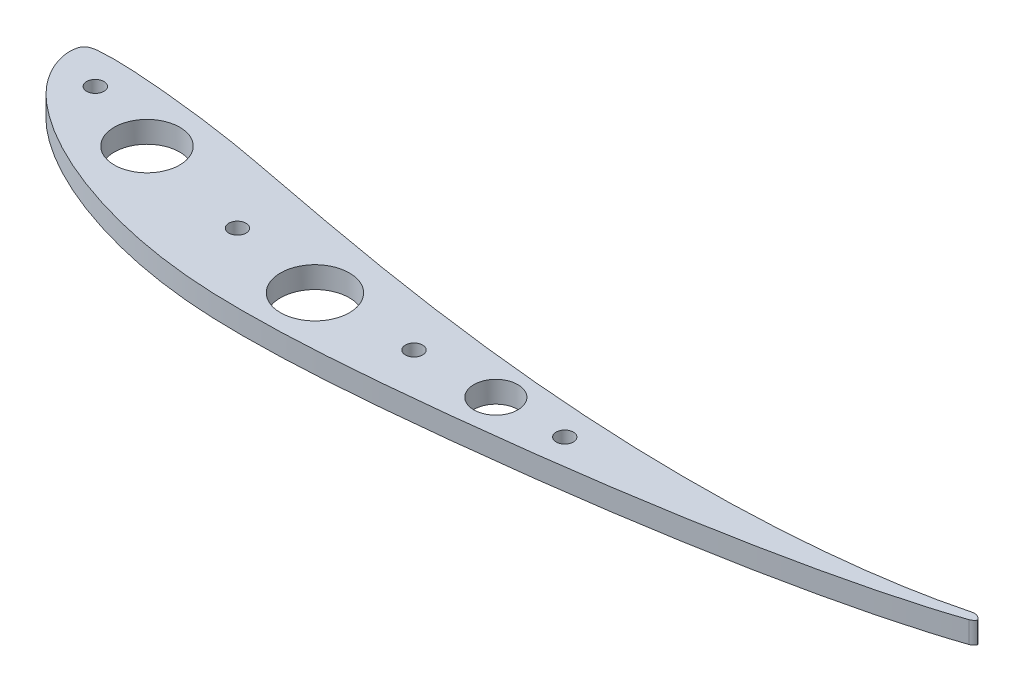
SolidWorks part; units mm, degrees
material "6061-T6 (SS)"
ref_plane "Front Plane" through (0, 0, 0) normal (0, 0, 1) x (1, 0, 0)
ref_plane "Top Plane" through (0, 0, 0) normal (0, 1, 0) x (1, 0, 0)
ref_plane "Right Plane" through (0, 0, 0) normal (1, 0, 0) x (0, 0, -1)
curve "Curve1"
  spline degree 3 poles (-3.7953, 0, -0.0099) (-3.8135, 0, 0.0025) (-3.7975, 0, -0.0094) (-3.7869, 0, -0.0198) (-3.7634, 0, -0.0415) (-3.7356, 0, -0.0646) (-3.6977, 0, -0.0879) (-3.6505, 0, -0.1105) (-3.5935, 0, -0.134) (-3.5268, 0, -0.1582) (-3.4508, 0, -0.1829) (-3.3657, 0, -0.2079) (-3.2722, 0, -0.233) (-3.1706, 0, -0.258) (-3.0616, 0, -0.2828) (-2.9459, 0, -0.3071) (-2.8241, 0, -0.331) (-2.697, 0, -0.354) (-2.5653, 0, -0.3761) (-2.4298, 0, -0.3971) (-2.2915, 0, -0.417) (-2.1511, 0, -0.4356) (-2.0096, 0, -0.4529) (-1.8684, 0, -0.4689) (-1.7284, 0, -0.4834) (-1.5908, 0, -0.496) (-1.4567, 0, -0.506) (-1.3267, 0, -0.5129) (-1.2016, 0, -0.5159) (-1.082, 0, -0.5155) (-0.9682, 0, -0.5097) (-0.8601, 0, -0.4978) (-0.7573, 0, -0.4811) (-0.6597, 0, -0.4593) (-0.5675, 0, -0.4338) (-0.481, 0, -0.4051) (-0.4006, 0, -0.3736) (-0.3268, 0, -0.3398) (-0.2599, 0, -0.3041) (-0.2001, 0, -0.2671) (-0.148, 0, -0.2293) (-0.1034, 0, -0.1913) (-0.0671, 0, -0.1529) (-0.0392, 0, -0.1144) (-0.0186, 0, -0.0769) (-0.0054, 0, -0.0412) (0.0009, 0, -0.0084) (-0.0003, 0, 0.0194) (-0.0075, 0, 0.0449) (-0.0341, 0, 0.0576) (-0.0699, 0, 0.0593) (-0.1188, 0, 0.0611) (-0.1803, 0, 0.0584) (-0.2538, 0, 0.0535) (-0.3383, 0, 0.0457) (-0.433, 0, 0.0352) (-0.5376, 0, 0.0216) (-0.6518, 0, 0.0027) (-0.7763, 0, -0.0211) (-0.9117, 0, -0.0469) (-1.0573, 0, -0.0742) (-1.2123, 0, -0.1018) (-1.3754, 0, -0.1287) (-1.5454, 0, -0.154) (-1.7209, 0, -0.1767) (-1.9002, 0, -0.1962) (-2.0817, 0, -0.2116) (-2.2636, 0, -0.2225) (-2.4439, 0, -0.2285) (-2.6207, 0, -0.2293) (-2.792, 0, -0.2247) (-2.9559, 0, -0.215) (-3.1104, 0, -0.2002) (-3.2537, 0, -0.1809) (-3.3838, 0, -0.1577) (-3.4993, 0, -0.1313) (-3.598, 0, -0.103) (-3.6788, 0, -0.0729) (-3.7364, 0, -0.0453) (-3.7789, 0, -0.0198) (-3.7953, 0, -0.0099) (-3.8135, 0, 0.0025) (-3.7975, 0, -0.0094) knots -0.009748 -0.004147 -0.001 0 0.00098 0.003649 0.007483 0.012095 0.017526 0.024052 0.031783 0.040678 0.05071 0.061833 0.073989 0.087118 0.101145 0.115991 0.13157 0.147788 0.164551 0.181758 0.199312 0.217095 0.23499 0.252857 0.270541 0.287887 0.304773 0.321101 0.336806 0.3518 0.366031 0.379616 0.392653 0.40517 0.417172 0.428604 0.439419 0.449597 0.459102 0.467908 0.475988 0.483309 0.489875 0.495803 0.501149 0.505903 0.510047 0.513579 0.516447 0.51935 0.523823 0.529974 0.537716 0.546968 0.557637 0.56962 0.582804 0.597247 0.613135 0.630444 0.649056 0.668822 0.689595 0.71119 0.733427 0.756094 0.778989 0.80189 0.824567 0.846792 0.868338 0.888978 0.908492 0.926659 0.943286 0.958169 0.971136 0.981956 0.990252 0.995853 0.999 1 1.00098 1.003649 1.007483 periodic
sketch "Sketch1" plane through (0, 0, 0) normal (0, 1, 0) x (1, 0, 0)
  line L0 (300, 0) -> (0, 0) construction
  line L1 (0, -0.0038) -> (0, 31241.5392) construction
  spline S1 degree 3 poles (299.0159, -0.7428) (300.2719, 0.1937) (298.8393, -0.7794) (297.5541, -1.5573) (294.2085, -3.5672) (289.6705, -5.7413) (283.3099, -8.1175) (275.5375, -10.3446) (266.4449, -12.4265) (256.1996, -14.2599) (244.9216, -15.7834) (232.7578, -16.953) (219.853, -17.7239) (206.3624, -18.0861) (192.4404, -18.0311) (178.2424, -17.5631) (163.9225, -16.7077) (149.6301, -15.4991) (135.5088, -13.9687) (121.6919, -12.1854) (108.3038, -10.2012) (95.4598, -8.0891) (83.2597, -5.9197) (71.7929, -3.7745) (61.1316, -1.7428) (51.3278, 0.1241) (42.3328, 1.6125) (34.1026, 2.6768) (26.6412, 3.5063) (19.985, 4.119) (14.2022, 4.501) (9.357, 4.7083) (5.5043, 4.5714) (2.688, 4.4306) (0.5936, 3.4334) (0.0308, 1.4257) (-0.0641, -0.7632) (0.4323, -3.351) (1.473, -6.1545) (3.0963, -9.1071) (5.2936, -12.1419) (8.1539, -15.1651) (11.6635, -18.1507) (15.7717, -21.1312) (20.4766, -24.0434) (25.7488, -26.8479) (31.5595, -29.5127) (37.8902, -31.9837) (44.7015, -34.2477) (51.9643, -36.2517) (59.6481, -37.9602) (67.7447, -39.2782) (76.2563, -40.2093) (85.2174, -40.6672) (94.6314, -40.6888) (104.481, -40.4514) (114.7156, -39.906) (125.2783, -39.1146) (136.1088, -38.1192) (147.1308, -36.9759) (158.2548, -35.7058) (169.3884, -34.3411) (180.4428, -32.872) (191.3379, -31.3034) (202.0038, -29.6476) (212.3716, -27.9014) (222.3815, -26.0873) (231.9704, -24.2079) (241.0824, -22.2863) (249.6618, -20.3324) (257.6575, -18.3584) (265.0236, -16.3786) (271.7194, -14.4111) (277.7075, -12.4652) (282.9568, -10.5577) (287.4427, -8.7022) (291.1585, -6.9245) (294.1466, -5.0904) (296.3308, -3.2713) (298.1821, -1.5614) (299.0159, -0.7428) (300.2719, 0.1937) (298.8393, -0.7794) knots -0.007483 -0.003649 -0.00098 0 0.001 0.004147 0.009748 0.018044 0.028864 0.041831 0.056714 0.073341 0.091508 0.111022 0.131662 0.153208 0.175433 0.19811 0.221011 0.243906 0.266573 0.28881 0.310405 0.331178 0.350944 0.369556 0.386865 0.402753 0.417196 0.43038 0.442363 0.453032 0.462284 0.470026 0.476177 0.48065 0.483553 0.486421 0.489953 0.494097 0.498851 0.504197 0.510125 0.516691 0.524012 0.532092 0.540898 0.550403 0.560581 0.571396 0.582828 0.59483 0.607347 0.620384 0.633969 0.6482 0.663194 0.678899 0.695227 0.712113 0.729459 0.747143 0.76501 0.782905 0.800688 0.818242 0.835449 0.852212 0.86843 0.884009 0.898855 0.912882 0.926011 0.938167 0.94929 0.959322 0.968217 0.975948 0.982474 0.987905 0.992517 0.996351 0.99902 1 1.001 1.004147 1.009748 only from (300, 0) to (300, 0)
  dimension "D1" = 300
extrude "Boss-Extrude1" add sketch "Sketch1" along normal blind 6.35
sketch "Sketch2" plane through (0, 6.35, 0) normal (0, 1, 0) x (1, 0, 0)
  line L1 (279.4, 165.8903) -> (673.2029, 165.8903)
  line L2 (279.4, 165.8903) -> (279.4, -211.3983)
  line L3 (279.4, -211.3983) -> (673.2029, -211.3983)
  line L4 (673.2029, 165.8903) -> (673.2029, -211.3983)
  line L5 (476.3015, -211.3983) -> (476.3015, 165.8903) construction
  line L6 (279.4, -22.754) -> (673.2029, -22.754) construction
  point P204 (476.3015, -22.754)
  dimension "D1" = 279.4
extrude "Cut-Extrude1" cut sketch "Sketch2" against normal through all both and the other way through all
sketch "Sketch3" plane through (0, 6.35, 0) normal (0, 1, 0) x (1, 0, 0)
  line L0 (-1000, 0) -> (49000, 0) construction
  line L1 (35.56, -12.7) -> (35.56, 0) construction
  line L2 (151.13, -25.4) -> (151.13, 0) construction
  line L3 (97.79, -25.4) -> (97.79, 0) construction
  circle A0 centre (35.56, -12.7) radius 9.652
  circle A1 centre (151.13, -25.4) radius 6.477
  circle A2 centre (97.79, -25.4) radius 10.16
  dimension "D1" = 19.304
  dimension "D2" = 12.954
  dimension "D7" = 20.32
  dimension "D3" = 35.56
  dimension "D4" = 12.7
  dimension "D5" = 25.4
  dimension "D6" = 151.13
  dimension "D8" = 97.79
  dimension "D9" = 25.4
extrude "Cut-Extrude2" cut sketch "Sketch3" against normal through all both and the other way through all
sketch "Sketch4" plane through (0, 6.35, 0) normal (0, 1, 0) x (1, 0, 0)
  line L0 (-1000, 0) -> (49000, 0) construction
  line L1 (12.7, -5.08) -> (12.7, 0) construction
  line L2 (69.85, -20.32) -> (69.85, 0) construction
  line L3 (127, -25.4) -> (127, 0) construction
  line L4 (171.45, -25.4) -> (171.45, 0) construction
  circle A0 centre (12.7, -5.08) radius 2.54
  circle A1 centre (69.85, -20.32) radius 2.54
  circle A2 centre (127, -25.4) radius 2.54
  circle A3 centre (171.45, -25.4) radius 2.54
  dimension "D5" = 5.08
  dimension "D1" = 25.4
  dimension "D2" = 25.4
  dimension "D3" = 20.32
  dimension "D4" = 5.08
  dimension "D6" = 12.7
  dimension "D7" = 69.85
  dimension "D8" = 127
  dimension "D9" = 171.45
extrude "Cut-Extrude3" cut sketch "Sketch4" against normal through all both and the other way through all
fillet "Fillet1" radius 2.54 2 edges at (279.4, 3.175, 11.8372) (279.4, 3.175, 9.2149)
